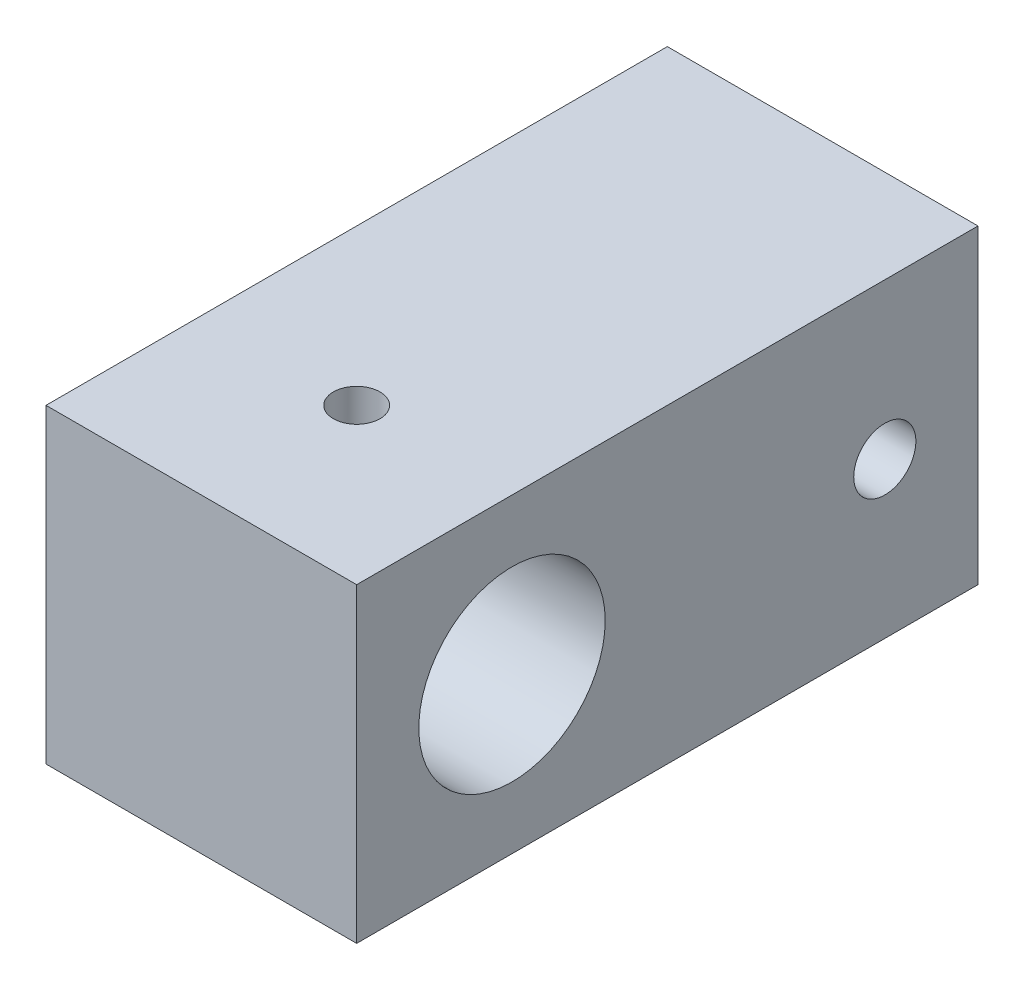
SolidWorks part; units mm, degrees
ref_plane "Płaszczyzna przednia" through (0, 0, 0) normal (0, 0, 1) x (1, 0, 0)
ref_plane "Płaszczyzna górna" through (0, 0, 0) normal (0, 1, 0) x (1, 0, 0)
ref_plane "Płaszczyzna prawa" through (0, 0, 0) normal (1, 0, 0) x (0, 0, -1)
sketch "Sketch1" plane through (0, 0, 0) normal (0, 0, 1) x (1, 0, 0)
  line L1 (0, 0) -> (20, 0)
  line L2 (0, 0) -> (0, 20)
  line L3 (0, 20) -> (20, 20)
  line L4 (20, 0) -> (20, 20)
  line L5 (0, 0) -> (20, 20) construction
  line L6 (0, 20) -> (20, 0) construction
  point P4 (10, 10)
  dimension "D1" = 20
  dimension "D2" = 20
extrude "Boss-Extrude1" add sketch "Sketch1" along normal blind 40
sketch "Sketch2" plane through (20, 0, 0) normal (1, 0, 0) x (0, 0, -1)
  line L0 (-40, 0) -> (-40, 20) construction
  line L1 (-40, 0) -> (0, 0) construction
  circle A0 centre (-30, 10) radius 6
  dimension "D1" = 12
  dimension "D2" = 10
  dimension "D3" = 10
extrude "Cut-Extrude1" cut sketch "Sketch2" against normal blind 30
hole_wizard "Ø3.0mm Dowel Hole1" positions "Sketch3" profile "Sketch4" hole size "Ø3.0" standard "ANSI Metric" end condition up to next
sketch "Sketch3" plane through (0, 20, 0) normal (0, 1, 0) x (1, 0, 0)
  line L0 (20, -40) -> (20, 0) construction
  line L2 (20, -40) -> (0, -40) construction
  point P0 (10, -30)
  point P9 (14.1293, -30)
  dimension "D1" = 10
  dimension "D2" = 10
sketch "Sketch4" plane through (10, 20, 30) normal (1, 0, 0) x (0, 0, 1)
  line L0 (0, 0) -> (0, 4)
  line L1 (0, 4) -> (1.5, 4)
  line L2 (1.5, 4) -> (1.5, 0)
  line L5 (1.5, 0) -> (0, 0)
  line L11 (0, -6.35) -> (0, 107.95) construction
  dimension "Thru Hole Dia." = 3
  dimension "Thru Hole Depth" = 4
sketch "Sketch5" plane through (0, 0, 0) normal (-1, 0, 0) x (0, 0, 1)
  line L0 (0, 20) -> (0, 0) construction
  line L1 (40, 0) -> (0, 0) construction
  circle A0 centre (6, 10) radius 2
  dimension "D1" = 4
  dimension "D2" = 6
  dimension "D3" = 10
extrude "Cut-Extrude2" cut sketch "Sketch5" against normal blind 30
